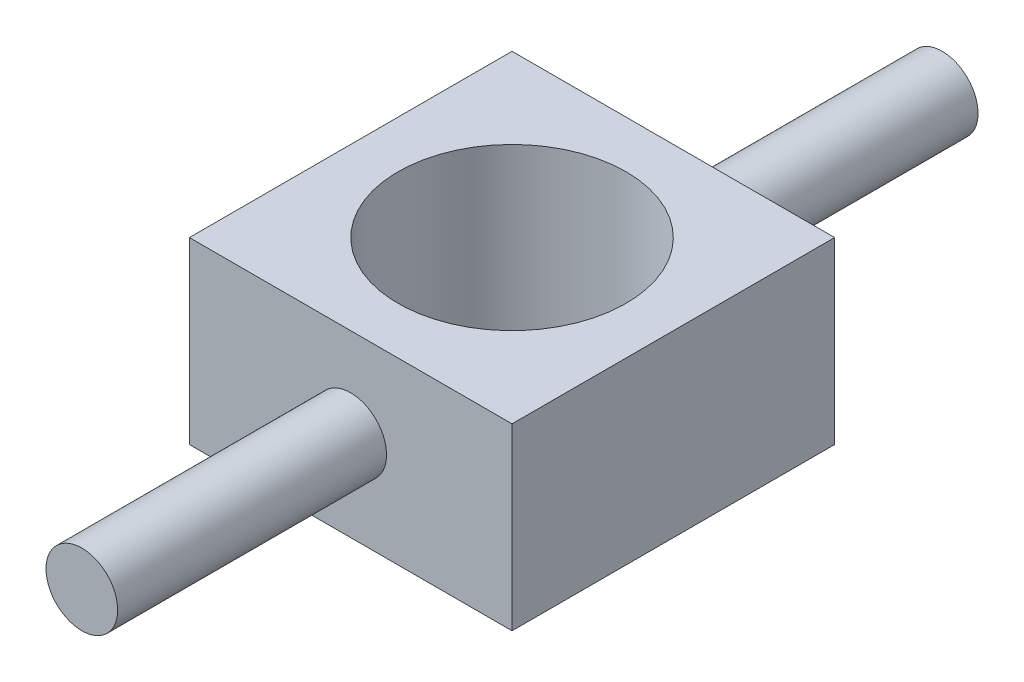
SolidWorks part; units mm, degrees
ref_plane "Front Plane" through (0, 0, 0) normal (0, 0, 1) x (1, 0, 0)
ref_plane "Top Plane" through (0, 0, 0) normal (0, 1, 0) x (1, 0, 0)
ref_plane "Right Plane" through (0, 0, 0) normal (1, 0, 0) x (0, 0, -1)
sketch "Sketch1" plane through (0, 0, 0) normal (0, 1, 0) x (1, 0, 0)
  line L1 (-18, 18) -> (18, 18)
  line L2 (-18, 18) -> (-18, -18)
  line L3 (-18, -18) -> (18, -18)
  line L4 (18, 18) -> (18, -18)
  line L5 (-18, 18) -> (18, -18) construction
  line L6 (-18, -18) -> (18, 18) construction
  point P0 (0, 0)
  dimension "D1" = 36
  dimension "D2" = 36
extrude "Boss-Extrude1" add sketch "Sketch1" along normal blind 10 and the other way blind 10
sketch "Sketch2" plane through (0, -10, 0) normal (0, -1, 0) x (1, 0, 0)
  circle A0 centre (0, 0) radius 12.725
  dimension "D1" = 25.45
extrude "Cut-Extrude1" cut sketch "Sketch2" against normal through all
sketch "Sketch5" plane through (0, 0, -18) normal (0, 0, -1) x (-1, 0, 0)
  circle A0 centre (0, 0) radius 4
  dimension "D1" = 8
extrude "Boss-Extrude2" add sketch "Sketch5" along normal blind 30
mirror "Mirror1" about plane through (0, 0, 0) normal (0, 0, 1) of "Boss-Extrude2"
